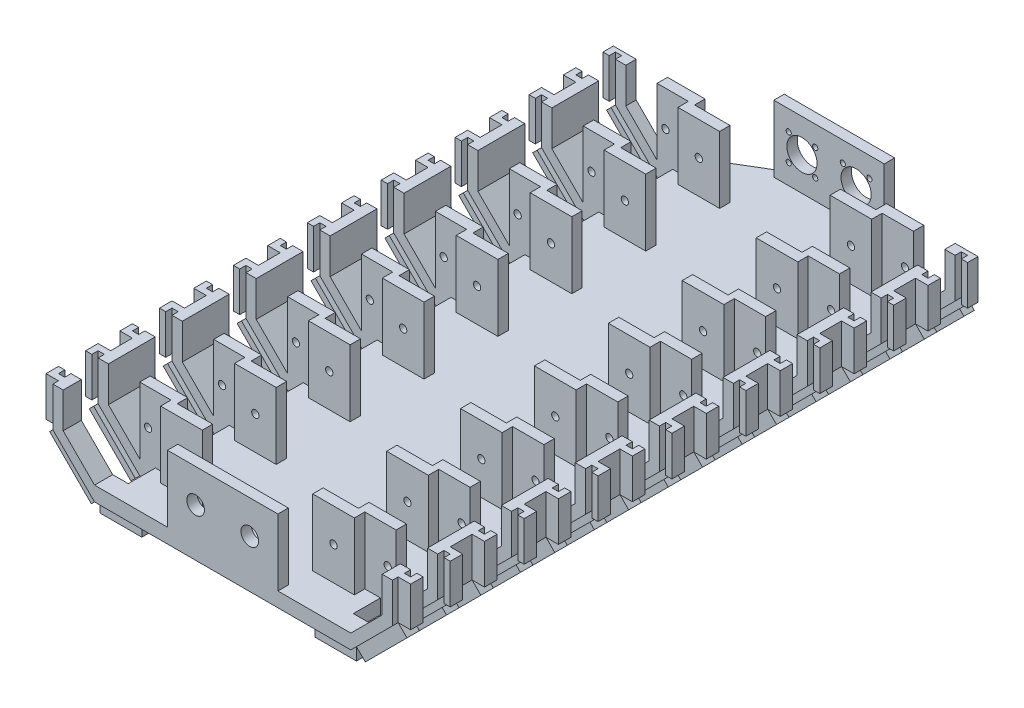
SolidWorks part; units mm, degrees
ref_plane "Front Plane" through (0, 0, 0) normal (0, 0, 1) x (1, 0, 0)
ref_plane "Top Plane" through (0, 0, 0) normal (0, 1, 0) x (1, 0, 0)
ref_plane "Right Plane" through (0, 0, 0) normal (1, 0, 0) x (0, 0, -1)
sketch "Sketch1" plane through (0, 0, 0) normal (0, 1, 0) x (1, 0, 0)
  line L0 (0, -135) -> (0, 135) construction
  line L1 (-13, 135) -> (-36, 135)
  line L2 (13, -135) -> (-13, -135)
  line L3 (13, -135) -> (13, 135) construction
  line L4 (13, 135) -> (-13, 135)
  line L5 (-13, -135) -> (-13, 135) construction
  line L8 (-36, 135) -> (-36, -135) construction
  line L9 (-36, -135) -> (-13, -135)
  line L10 (-36, 135) -> (-61.5, 135)
  line L11 (-61.5, 135) -> (-61.5, -135)
  line L12 (-61.5, -135) -> (-36, -135)
  line L13 (36, -135) -> (13, -135)
  line L14 (61.5, -135) -> (36, -135)
  line L15 (61.5, 135) -> (61.5, -135)
  line L16 (36, 135) -> (36, -135) construction
  line L17 (13, 135) -> (36, 135)
  line L18 (36, 135) -> (61.5, 135)
  point P0 (0, 0)
  point P4 (0, 0)
  dimension "D1" = 270
  dimension "D2" = 26
  dimension "D3" = 23
  dimension "D4" = 123
extrude "Boss-Extrude1" add sketch "Sketch1" along normal blind 7
sketch "Sketch2" plane through (0, 7, 0) normal (0, 1, 0) x (1, 0, 0)
  line L0 (61.5, -135) -> (61.5, 135) construction
  line L1 (-61.5, -135) -> (61.5, -135)
  line L2 (-61.5, -135) -> (-61.5, -130)
  line L3 (-61.5, -130) -> (61.5, -130)
  line L4 (61.5, -135) -> (61.5, -130)
  line L5 (-61.5, 135) -> (-36.5, 135) construction
  line L6 (-61.5, 135) -> (61.5, 135) construction
  line L7 (-61.5, 135) -> (-61.5, 130) construction
  line L8 (-61.5, 130) -> (61.5, 130) construction
  line L9 (61.5, 135) -> (61.5, 130) construction
  line L10 (-36.5, 135) -> (-26.5, 135)
  line L11 (-36.5, 135) -> (-46.5, 135)
  line L12 (-46.5, 135) -> (-46.5, 130)
  line L13 (-46.5, 130) -> (-26.5, 130)
  line L14 (-26.5, 130) -> (-26.5, 135)
  line L15 (0, 135) -> (0, 130) construction
  line L16 (46.5, 130) -> (26.5, 130)
  line L17 (46.5, 135) -> (46.5, 130)
  line L18 (36.5, 135) -> (46.5, 135)
  line L19 (36.5, 135) -> (26.5, 135)
  line L20 (26.5, 130) -> (26.5, 135)
  line L21 (-26.5, 130) -> (-26.5, -130) construction
  dimension "D1" = 5
  dimension "D2" = 5
  dimension "D3" = 25
  dimension "D4" = 10
  dimension "D5" = 10
extrude "Boss-Extrude2" add sketch "Sketch2" along normal blind 32
sketch "Sketch3" plane through (0, 0, 135) normal (0, 0, 1) x (1, 0, 0)
  line L0 (0, 39) -> (0, 0) construction
  line L2 (-61.5, 39) -> (-61.5, 7) construction
  line L3 (-61.5, 39) -> (61.5, 39) construction
  line L5 (-61.5, 39) -> (-61.5, 0) construction
  line L6 (-61.5, 23) -> (61.5, 23) construction
  line L7 (61.5, 39) -> (61.5, 0) construction
  circle A0 centre (-13, 23) radius 4.25
  circle A1 centre (13, 23) radius 4.25
  dimension "D1" = 8.5
  dimension "D2" = 8.5
  dimension "D3" = 26
  dimension "D4" = 13
  dimension "D5" = 32
  dimension "D6" = 16
sketch "Sketch8" plane through (0, 0, -130) normal (0, 0, 1) x (1, 0, 0)
  line L0 (0, 39) -> (0, 7) construction
  line L2 (0, 23) -> (-61.5, 23) construction
  line L3 (-61.5, 39) -> (-61.5, 0) construction
  line L4 (-36.5, 39) -> (-36.5, 7) construction
  line L5 (-46.5, 39) -> (-26.5, 39) construction
  line L6 (-46.5, 7) -> (-26.5, 7) construction
  line L7 (-61.5, 39) -> (61.5, 39) construction
  circle A0 centre (-36.5, 23) radius 1.75
  circle A1 centre (36.5, 23) radius 1.75
  dimension "D2" = 3.5
  dimension "D1" = 32
sketch "Sketch9" plane through (0, 0, -135) normal (0, 0, -1) x (-1, 0, 0)
  line L1 (-61.5, 7) -> (61.5, 7)
  line L2 (-61.5, 7) -> (-61.5, 0)
  line L3 (-61.5, 0) -> (61.5, 0)
  line L4 (61.5, 7) -> (61.5, 0)
extrude "Boss-Extrude4" add sketch "Sketch9" along normal blind 5
sketch "Sketch10" plane through (0, 7, 0) normal (0, 1, 0) x (1, 0, 0)
  line L0 (-26.5, 135) -> (-46.5, 135) construction
  line L1 (-61.5, 140) -> (-43.5, 140)
  line L2 (-61.5, 140) -> (-61.5, 135)
  line L3 (-61.5, 135) -> (-43.5, 135)
  line L4 (-43.5, 140) -> (-43.5, 135)
  line L5 (26.5, 135) -> (46.5, 135) construction
  line L6 (61.5, 140) -> (43.5, 140)
  line L7 (61.5, 140) -> (61.5, 135)
  line L8 (61.5, 135) -> (43.5, 135)
  line L9 (43.5, 140) -> (43.5, 135)
  line L10 (-46.5, 135) -> (-46.5, 130) construction
  line L11 (46.5, 130) -> (46.5, 135) construction
  dimension "D1" = 3
  dimension "D2" = 3
extrude "Boss-Extrude8" add sketch "Sketch10" along normal blind 32
sketch "Sketch11" plane through (0, 7, 0) normal (0, 1, 0) x (1, 0, 0)
  line L0 (0, 140) -> (0, -130) construction
  line L1 (-43.5, 140) -> (43.5, 140) construction
  line L2 (61.5, -130) -> (-61.5, -130) construction
  line L3 (-61.5, 140) -> (-61.5, 135) construction
  line L4 (-61.5, 135) -> (-46.5, 135) construction
  line L5 (-46.5, 135) -> (-46.5, 130) construction
  line L6 (-46.5, 130) -> (-26.5, 130) construction
  line L7 (-26.5, 130) -> (-26.5, 135) construction
  line L8 (-26.5, 135) -> (-43.5, 135) construction
  line L9 (-43.5, 135) -> (-43.5, 140) construction
  line L10 (-43.5, 140) -> (-61.5, 140) construction
  line L11 (-26.5, -130) -> (-26.5, -109.8199)
  line L12 (-43.5, 104.5294) -> (-61.5, 104.5294)
  line L13 (-61.5, 104.5294) -> (-61.5, 99.5294)
  line L14 (-61.5, 99.5294) -> (-46.5, 99.5294)
  line L15 (-46.5, 99.5294) -> (-46.5, 94.5294)
  line L16 (-46.5, 94.5294) -> (-26.5, 94.5294)
  line L17 (-26.5, 94.5294) -> (-26.5, 99.5294)
  line L18 (-26.5, 99.5294) -> (-43.5, 99.5294)
  line L19 (-43.5, 99.5294) -> (-43.5, 104.5294)
  line L20 (-43.5, 69.0588) -> (-61.5, 69.0588)
  line L21 (-61.5, 69.0588) -> (-61.5, 64.0588)
  line L22 (-61.5, 64.0588) -> (-46.5, 64.0588)
  line L23 (-46.5, 64.0588) -> (-46.5, 59.0588)
  line L24 (-46.5, 59.0588) -> (-26.5, 59.0588)
  line L25 (-26.5, 59.0588) -> (-26.5, 64.0588)
  line L26 (-26.5, 64.0588) -> (-43.5, 64.0588)
  line L27 (-43.5, 64.0588) -> (-43.5, 69.0588)
  line L28 (-43.5, 33.5882) -> (-61.5, 33.5882)
  line L29 (-61.5, 33.5882) -> (-61.5, 28.5882)
  line L30 (-61.5, 28.5882) -> (-46.5, 28.5882)
  line L31 (-46.5, 28.5882) -> (-46.5, 23.5882)
  line L32 (-46.5, 23.5882) -> (-26.5, 23.5882)
  line L33 (-26.5, 23.5882) -> (-26.5, 28.5882)
  line L34 (-26.5, 28.5882) -> (-43.5, 28.5882)
  line L35 (-43.5, 28.5882) -> (-43.5, 33.5882)
  line L36 (-43.5, -1.8824) -> (-61.5, -1.8824)
  line L37 (-61.5, -1.8824) -> (-61.5, -6.8824)
  line L38 (-61.5, -6.8824) -> (-46.5, -6.8824)
  line L39 (-46.5, -6.8824) -> (-46.5, -11.8824)
  line L40 (-46.5, -11.8824) -> (-26.5, -11.8824)
  line L41 (-26.5, -11.8824) -> (-26.5, -6.8824)
  line L42 (-26.5, -6.8824) -> (-43.5, -6.8824)
  line L43 (-43.5, -6.8824) -> (-43.5, -1.8824)
  line L44 (-43.5, -37.3529) -> (-61.5, -37.3529)
  line L45 (-61.5, -37.3529) -> (-61.5, -42.3529)
  line L46 (-61.5, -42.3529) -> (-46.5, -42.3529)
  line L47 (-46.5, -42.3529) -> (-46.5, -47.3529)
  line L48 (-46.5, -47.3529) -> (-26.5, -47.3529)
  line L49 (-26.5, -47.3529) -> (-26.5, -42.3529)
  line L50 (-26.5, -42.3529) -> (-43.5, -42.3529)
  line L51 (-43.5, -42.3529) -> (-43.5, -37.3529)
  line L52 (-43.5, -72.8235) -> (-61.5, -72.8235)
  line L53 (-61.5, -72.8235) -> (-61.5, -77.8235)
  line L54 (-61.5, -77.8235) -> (-46.5, -77.8235)
  line L55 (-46.5, -77.8235) -> (-46.5, -82.8235)
  line L56 (-46.5, -82.8235) -> (-26.5, -82.8235)
  line L57 (-26.5, -82.8235) -> (-26.5, -77.8235)
  line L58 (-26.5, -77.8235) -> (-43.5, -77.8235)
  line L59 (-43.5, -77.8235) -> (-43.5, -72.8235)
  line L60 (-43.5, -108.2941) -> (-61.5, -108.2941)
  line L61 (-61.5, -108.2941) -> (-61.5, -113.2941)
  line L62 (-61.5, -113.2941) -> (-46.5, -113.2941)
  line L63 (-46.5, -113.2941) -> (-46.5, -118.2941)
  line L64 (-46.5, -118.2941) -> (-26.5, -118.2941)
  line L65 (-26.5, -118.2941) -> (-26.5, -113.2941)
  line L66 (-26.5, -113.2941) -> (-43.5, -113.2941)
  line L67 (-43.5, -113.2941) -> (-43.5, -108.2941)
  line L68 (43.5, -113.2941) -> (43.5, -108.2941)
  line L69 (26.5, -113.2941) -> (43.5, -113.2941)
  line L70 (26.5, -118.2941) -> (26.5, -113.2941)
  line L71 (46.5, -118.2941) -> (26.5, -118.2941)
  line L72 (46.5, -113.2941) -> (46.5, -118.2941)
  line L73 (61.5, -113.2941) -> (46.5, -113.2941)
  line L74 (61.5, -108.2941) -> (61.5, -113.2941)
  line L75 (43.5, -108.2941) -> (61.5, -108.2941)
  line L76 (43.5, -77.8235) -> (43.5, -72.8235)
  line L77 (26.5, -77.8235) -> (43.5, -77.8235)
  line L78 (26.5, -82.8235) -> (26.5, -77.8235)
  line L79 (46.5, -82.8235) -> (26.5, -82.8235)
  line L80 (46.5, -77.8235) -> (46.5, -82.8235)
  line L81 (61.5, -77.8235) -> (46.5, -77.8235)
  line L82 (61.5, -72.8235) -> (61.5, -77.8235)
  line L83 (43.5, -72.8235) -> (61.5, -72.8235)
  line L84 (43.5, -42.3529) -> (43.5, -37.3529)
  line L85 (26.5, -42.3529) -> (43.5, -42.3529)
  line L86 (26.5, -47.3529) -> (26.5, -42.3529)
  line L87 (46.5, -47.3529) -> (26.5, -47.3529)
  line L88 (46.5, -42.3529) -> (46.5, -47.3529)
  line L89 (61.5, -42.3529) -> (46.5, -42.3529)
  line L90 (61.5, -37.3529) -> (61.5, -42.3529)
  line L91 (43.5, -37.3529) -> (61.5, -37.3529)
  line L92 (43.5, -6.8824) -> (43.5, -1.8824)
  line L93 (26.5, -6.8824) -> (43.5, -6.8824)
  line L94 (26.5, -11.8824) -> (26.5, -6.8824)
  line L95 (46.5, -11.8824) -> (26.5, -11.8824)
  line L96 (46.5, -6.8824) -> (46.5, -11.8824)
  line L97 (61.5, -6.8824) -> (46.5, -6.8824)
  line L98 (61.5, -1.8824) -> (61.5, -6.8824)
  line L99 (43.5, -1.8824) -> (61.5, -1.8824)
  line L100 (43.5, 28.5882) -> (43.5, 33.5882)
  line L101 (26.5, 28.5882) -> (43.5, 28.5882)
  line L102 (26.5, 23.5882) -> (26.5, 28.5882)
  line L103 (46.5, 23.5882) -> (26.5, 23.5882)
  line L104 (46.5, 28.5882) -> (46.5, 23.5882)
  line L105 (61.5, 28.5882) -> (46.5, 28.5882)
  line L106 (61.5, 33.5882) -> (61.5, 28.5882)
  line L107 (43.5, 33.5882) -> (61.5, 33.5882)
  line L108 (43.5, 64.0588) -> (43.5, 69.0588)
  line L109 (26.5, 64.0588) -> (43.5, 64.0588)
  line L110 (26.5, 59.0588) -> (26.5, 64.0588)
  line L111 (46.5, 59.0588) -> (26.5, 59.0588)
  line L112 (46.5, 64.0588) -> (46.5, 59.0588)
  line L113 (61.5, 64.0588) -> (46.5, 64.0588)
  line L114 (61.5, 69.0588) -> (61.5, 64.0588)
  line L115 (43.5, 69.0588) -> (61.5, 69.0588)
  line L116 (43.5, 99.5294) -> (43.5, 104.5294)
  line L117 (26.5, 99.5294) -> (43.5, 99.5294)
  line L118 (26.5, 94.5294) -> (26.5, 99.5294)
  line L119 (46.5, 94.5294) -> (26.5, 94.5294)
  line L120 (46.5, 99.5294) -> (46.5, 94.5294)
  line L121 (61.5, 99.5294) -> (46.5, 99.5294)
  line L122 (61.5, 104.5294) -> (61.5, 99.5294)
  line L123 (43.5, 104.5294) -> (61.5, 104.5294)
  point P136 (-54, 135)
  line M11 (-61.5, 135) -> (-61.5, -130)
  line M13 (61.5, -130) -> (61.5, 135)
  dimension "D1" = 20.1801
  dimension "D3" = 30.4706
  dimension "D2" = 8
extrude "Boss-Extrude9" add sketch "Sketch11" along normal blind 32 contours L18 L19 L12 L14 L15 L16 L17 M11 | L26 L27 L20 L22 L23 L24 L25 M11 | L34 L35 L28 L30 L31 L32 L33 M11 | L42 L43 L36 L38 L39 L40 L41 M11 | L50 L51 L44 L46 L47 L48 L49 M11 | L58 L59 L52 L54 L55 L56 L57 M11 | L66 L67 L60 L62 L63 L64 L11 M11 | L75 L68 L69 L70 L71 L72 L73 M13 | L83 L76 L77 L78 L79 L80 L81 M13 | L91 L84 L85 L86 L87 L88 L89 M13 | L107 L100 L101 L102 L103 L104 L105 M13 | L115 L108 L109 L110 L111 L112 L113 M13 | L123 L116 L117 L118 L119 L120 L121 M13 | L93 L92 L99 L98 L97 L96 L95 L94 region at (-44.0789, 7, 113.4257) region at (-44.0789, 7, -99.3978) region at (-44.0789, 7, -63.9272) region at (-44.0789, 7, -28.4567) region at (-44.0789, 7, 7.0139) region at (-44.0789, 7, 42.4845) region at (-44.0789, 7, 77.9551) region at (44.0789, 7, -99.3978) region at (44.0789, 7, -63.9272) region at (44.0789, 7, -28.4567) region at (44.0789, 7, 42.4845) region at (44.0789, 7, 77.9551) region at (44.0789, 7, 113.4257)
extrude "Cut-Extrude4" cut sketch "Sketch8" against normal blind 32 and the other way blind 250
sketch "Sketch13" plane through (0, 0, 135) normal (0, 0, 1) x (1, 0, 0)
  line L0 (-61.5, 39) -> (-61.5, 7)
  line L1 (-61.5, 39) -> (-61.5, 0) construction
  line L2 (-61.5, 39) -> (-26.5, 39)
  line L3 (-61.5, 39) -> (61.5, 39) construction
  line L4 (-26.5, 39) -> (-26.5, 7)
  line L5 (-26.5, 7) -> (-61.5, 7)
  line L6 (0, 39) -> (0, 5.5161) construction
  line L7 (26.5, 39) -> (26.5, 7)
  line L8 (61.5, 39) -> (26.5, 39)
  line L9 (61.5, 39) -> (61.5, 7)
  line L10 (26.5, 7) -> (61.5, 7)
  dimension "D1" = 32
  dimension "D2" = 35
extrude "Cut-Extrude5" cut sketch "Sketch13" against normal blind 11
sketch "Sketch14" plane through (0, 0, 135) normal (0, 0, 1) x (1, 0, 0)
  line L0 (0, 39) -> (0, 0) construction
  line L1 (-26.5, 39) -> (26.5, 39) construction
  line L2 (-81.5, 39) -> (0, 39) construction
  line L3 (-61.5, 0) -> (-81.5, 20)
  line L5 (-76.55, 22.05) -> (-61.5, 7)
  line L6 (-61.5, 39) -> (-61.5, 7) construction
  line L7 (-61.5, 7) -> (-61.5, 0)
  line L12 (-81.5, 20) -> (-81.5, 39)
  line L13 (-81.5, 39) -> (-76.55, 39)
  line L14 (-76.55, 39) -> (-76.55, 22.05)
  line L15 (76.55, 39) -> (76.55, 22.05)
  line L16 (81.5, 39) -> (76.55, 39)
  line L17 (81.5, 20) -> (81.5, 39)
  line L18 (61.5, 0) -> (81.5, 20)
  line L19 (61.5, 7) -> (61.5, 0)
  line L20 (76.55, 22.05) -> (61.5, 7)
  dimension "D1" = 28.2843
  dimension "D2" = 45
  dimension "D3" = 4.95
  dimension "D4" = 20
  dimension "D5" = 4.9497
extrude "Boss-Extrude10" add sketch "Sketch14" against normal blind 275
sketch "Sketch15" plane through (0, 7, 0) normal (0, 1, 0) x (1, 0, 0)
  line L0 (-54, 135) -> (-54, 122)
  line L1 (-61.5, 135) -> (-46.5, 135) construction
  line L2 (-54, 122) -> (-81.5, 122)
  line L4 (-81.5, 122) -> (-81.5, 135)
  line L5 (-81.5, 135) -> (-54, 135)
  line L6 (-81.5, 99.5294) -> (-54, 99.5294)
  line L7 (-54, 99.5294) -> (-54, 86.5294)
  line L8 (-54, 86.5294) -> (-81.5, 86.5294)
  line L9 (-81.5, 86.5294) -> (-81.5, 99.5294)
  line L10 (-81.5, 64.0588) -> (-54, 64.0588)
  line L11 (-54, 64.0588) -> (-54, 51.0588)
  line L12 (-54, 51.0588) -> (-81.5, 51.0588)
  line L13 (-81.5, 51.0588) -> (-81.5, 64.0588)
  line L14 (-81.5, 28.5882) -> (-54, 28.5882)
  line L15 (-54, 28.5882) -> (-54, 15.5882)
  line L16 (-54, 15.5882) -> (-81.5, 15.5882)
  line L17 (-81.5, 15.5882) -> (-81.5, 28.5882)
  line L18 (-81.5, -6.8824) -> (-54, -6.8824)
  line L19 (-54, -6.8824) -> (-54, -19.8824)
  line L20 (-54, -19.8824) -> (-81.5, -19.8824)
  line L21 (-81.5, -19.8824) -> (-81.5, -6.8824)
  line L22 (-81.5, -42.3529) -> (-54, -42.3529)
  line L23 (-54, -42.3529) -> (-54, -55.3529)
  line L24 (-54, -55.3529) -> (-81.5, -55.3529)
  line L25 (-81.5, -55.3529) -> (-81.5, -42.3529)
  line L26 (-81.5, -77.8235) -> (-54, -77.8235)
  line L27 (-54, -77.8235) -> (-54, -90.8235)
  line L28 (-54, -90.8235) -> (-81.5, -90.8235)
  line L29 (-81.5, -90.8235) -> (-81.5, -77.8235)
  line L30 (-81.5, -113.2941) -> (-54, -113.2941)
  line L31 (-54, -113.2941) -> (-54, -126.2941)
  line L32 (-54, -126.2941) -> (-81.5, -126.2941)
  line L33 (-81.5, -126.2941) -> (-81.5, -113.2941)
  line L34 (0, 140) -> (0, -135) construction
  line L35 (-43.5, 140) -> (43.5, 140) construction
  line L36 (-26.5, -135) -> (26.5, -135) construction
  line L37 (81.5, -126.2941) -> (81.5, -113.2941)
  line L38 (54, -126.2941) -> (81.5, -126.2941)
  line L39 (54, -113.2941) -> (54, -126.2941)
  line L40 (81.5, -113.2941) -> (54, -113.2941)
  line L41 (81.5, -90.8235) -> (81.5, -77.8235)
  line L42 (54, -90.8235) -> (81.5, -90.8235)
  line L43 (54, -77.8235) -> (54, -90.8235)
  line L44 (81.5, -77.8235) -> (54, -77.8235)
  line L45 (81.5, -55.3529) -> (81.5, -42.3529)
  line L46 (54, -55.3529) -> (81.5, -55.3529)
  line L47 (54, -42.3529) -> (54, -55.3529)
  line L48 (81.5, -42.3529) -> (54, -42.3529)
  line L49 (81.5, -19.8824) -> (81.5, -6.8824)
  line L50 (54, -19.8824) -> (81.5, -19.8824)
  line L51 (54, -6.8824) -> (54, -19.8824)
  line L52 (81.5, -6.8824) -> (54, -6.8824)
  line L53 (81.5, 15.5882) -> (81.5, 28.5882)
  line L54 (54, 15.5882) -> (81.5, 15.5882)
  line L55 (54, 28.5882) -> (54, 15.5882)
  line L56 (81.5, 28.5882) -> (54, 28.5882)
  line L57 (81.5, 51.0588) -> (81.5, 64.0588)
  line L58 (54, 51.0588) -> (81.5, 51.0588)
  line L59 (54, 64.0588) -> (54, 51.0588)
  line L60 (81.5, 64.0588) -> (54, 64.0588)
  line L61 (81.5, 86.5294) -> (81.5, 99.5294)
  line L62 (54, 86.5294) -> (81.5, 86.5294)
  line L63 (54, 99.5294) -> (54, 86.5294)
  line L64 (81.5, 99.5294) -> (54, 99.5294)
  line L65 (81.5, 122) -> (81.5, 135)
  line L66 (54, 122) -> (81.5, 122)
  line L67 (54, 135) -> (54, 122)
  line L68 (81.5, 135) -> (54, 135)
  line L69 (-61.5, -113.2941) -> (-46.5, -113.2941) construction
  line L70 (-81.5, 140) -> (-81.5, -135) construction
  dimension "D1" = 13
  dimension "D2" = 8
extrude "Cut-Extrude6" cut sketch "Sketch15" against normal through all both and the other way through all
sketch "Sketch16" plane through (0, 0, 113.2941) normal (0, 0, 1) x (1, 0, 0)
  line L0 (-61.5, 23) -> (0, 23) construction
  line L1 (-61.5, 39) -> (-61.5, 7) construction
  line L2 (0, 39) -> (0, 0) construction
  line L3 (-26.5, 39) -> (26.5, 39) construction
  circle A0 centre (-57.5, 22) radius 1.75
  circle A1 centre (57.5, 22) radius 1.75
  point P9 (-36.5, 23)
  dimension "D3" = 3.5
  dimension "D1" = 1
  dimension "D2" = 21
extrude "Cut-Extrude7" cut sketch "Sketch16" against normal through all both and the other way through all
sketch "Sketch17" plane through (0, 7, 0) normal (0, 1, 0) x (1, 0, 0)
  line L0 (-26.5, 130) -> (26.5, 130) construction
  line L1 (0, 130) -> (0, 161) construction
  line L2 (-26.5, -135) -> (-26.5, 161) construction
  line L3 (26.5, -135) -> (26.5, 161) construction
  line L4 (26.5, 161) -> (-26.5, 161) construction
  line L5 (0, 161) -> (0, 226) construction
  line L6 (-61.5, 140) -> (-26.5, 226)
  line L7 (-26.5, 226) -> (0, 226)
  line L8 (0, 226) -> (26.5, 226)
  line L9 (26.5, 226) -> (61.5, 140)
  line L10 (26.5, 161) -> (26.5, 226) construction
  line L11 (-26.5, 161) -> (-26.5, 226) construction
  line L12 (-61.5, 140) -> (61.5, 140)
  dimension "D1" = 31
  dimension "D2" = 296
  dimension "D3" = 90
  dimension "D4" = 65
extrude "Boss-Extrude13" add sketch "Sketch17" against normal blind 7 contours L12 L9 L8 L7 L6
sketch "Sketch18" plane through (0, 7, 0) normal (0, 1, 0) x (1, 0, 0)
  line L0 (-26.5, 130) -> (26.5, 130) construction
  line L1 (0, 130) -> (0, 161) construction
  line L2 (-26.5, 135) -> (-26.5, 161) construction
  line L3 (26.5, 135) -> (26.5, 161) construction
  line L4 (-26.5, 161) -> (-26.5, 156)
  line L5 (-26.5, 156) -> (26.5, 156)
  line L6 (26.5, 156) -> (26.5, 161)
  line L7 (26.5, 161) -> (-26.5, 161)
  dimension "D1" = 31
  dimension "D2" = 5
extrude "Boss-Extrude14" add sketch "Sketch18" along normal blind 32
extrude "Cut-Extrude8" cut sketch "Sketch3" against normal blind 334
sketch "Sketch19" plane through (0, 0, -156) normal (0, 0, 1) x (1, 0, 0)
  line L0 (0, 39) -> (0, 0) construction
  line L1 (-26.5, 39) -> (26.5, 39) construction
  line L3 (-6.636, 16.636) -> (-19.364, 16.636) construction
  line L4 (-6.636, 16.636) -> (-6.636, 29.364) construction
  line L5 (-6.636, 29.364) -> (-19.364, 29.364) construction
  line L6 (-19.364, 16.636) -> (-19.364, 29.364) construction
  line L7 (-6.636, 16.636) -> (-19.364, 29.364) construction
  line L8 (-6.636, 29.364) -> (-19.364, 16.636) construction
  circle A0 centre (-13, 23) radius 7.25
  circle A1 centre (-6.636, 16.636) radius 1.25
  circle A2 centre (-6.636, 29.364) radius 1.25
  circle A3 centre (-19.364, 29.364) radius 1.25
  circle A4 centre (-19.364, 16.636) radius 1.25
  circle A5 centre (13, 23) radius 7.25
  circle A6 centre (19.364, 16.636) radius 1.25
  circle A7 centre (6.636, 16.636) radius 1.25
  circle A8 centre (6.636, 29.364) radius 1.25
  circle A9 centre (19.364, 29.364) radius 1.25
  dimension "D1" = 14.5
  dimension "D4" = 2.5
  dimension "D5" = 2.5
  dimension "D6" = 2.5
  dimension "D7" = 2.5
  dimension "D2" = 18
  dimension "D3" = 18
  dimension "D8" = 12.7279
extrude "Cut-Extrude9" cut sketch "Sketch19" against normal blind 334
sketch "Sketch22" plane through (-30.75, -30.75, 0) normal (-0.7071, -0.7071, 0) x (0, 0, 1)
  line L0 (-138, 71.7713) -> (-138, 43.4871)
  line L1 (-140, 71.7713) -> (-135, 71.7713) construction
  line L2 (-140, 43.4871) -> (-135, 43.4871) construction
  line L3 (-140, 71.7713) -> (-140, 43.4871)
  line L4 (-135, 71.7713) -> (-135, 43.4871) construction
  line L5 (-138, 71.7713) -> (-140, 71.7713)
  line L6 (-140, 43.4871) -> (-226, 18.7383) construction
  line L7 (-140, 43.4871) -> (-138, 43.4871)
  line L8 (-119, 71.7713) -> (-119, 43.4871)
  line L9 (-122, 71.7713) -> (-99.5294, 71.7713) construction
  line L10 (-122, 43.4871) -> (-99.5294, 43.4871) construction
  line L11 (-119, 43.4871) -> (-116, 43.4871)
  line L12 (-116, 43.4871) -> (-116, 71.7713)
  line L13 (-116, 71.7713) -> (-119, 71.7713)
  line L14 (-122, 43.4871) -> (-122, 71.7713) construction
  line L15 (-99.5294, 71.7713) -> (-102.5294, 71.7713)
  line L16 (-102.5294, 71.7713) -> (-105.5294, 71.7713)
  line L17 (-105.5294, 71.7713) -> (-105.5294, 43.4871)
  line L18 (-105.5294, 43.4871) -> (-102.5294, 43.4871)
  line L19 (-102.5294, 43.4871) -> (-102.5294, 71.7713)
  line L20 (-86.5294, 71.7713) -> (-83.5294, 71.7713)
  line L21 (-86.5294, 71.7713) -> (-64.0588, 71.7713) construction
  line L22 (-83.5294, 71.7713) -> (-80.5294, 71.7713)
  line L23 (-80.5294, 71.7713) -> (-80.5294, 43.4871)
  line L24 (-86.5294, 43.4871) -> (-64.0588, 43.4871) construction
  line L25 (-80.5294, 43.4871) -> (-83.5294, 43.4871)
  line L26 (-83.5294, 43.4871) -> (-83.5294, 71.7713)
  line L27 (-67.0588, 71.7713) -> (-70.0588, 71.7713)
  line L28 (-70.0588, 71.7713) -> (-70.0588, 43.4871)
  line L29 (-70.0588, 43.4871) -> (-67.0588, 43.4871)
  line L30 (-67.0588, 43.4871) -> (-67.0588, 71.7713)
  line L31 (-48.0588, 71.7713) -> (-45.0588, 71.7713)
  line L32 (-45.0588, 71.7713) -> (-45.0588, 43.4871)
  line L33 (-45.0588, 43.4871) -> (-48.0588, 43.4871)
  line L34 (-48.0588, 43.4871) -> (-48.0588, 71.7713)
  line L35 (-31.5882, 71.7713) -> (-34.5882, 71.7713)
  line L36 (-34.5882, 71.7713) -> (-34.5882, 43.4871)
  line L37 (-34.5882, 43.4871) -> (-31.5882, 43.4871)
  line L38 (-31.5882, 43.4871) -> (-31.5882, 71.7713)
  line L39 (-12.5882, 71.7713) -> (-9.5882, 71.7713)
  line L40 (-9.5882, 71.7713) -> (-9.5882, 43.4871)
  line L41 (-9.5882, 43.4871) -> (-12.5882, 43.4871)
  line L42 (-12.5882, 43.4871) -> (-12.5882, 71.7713)
  line L43 (3.8824, 71.7713) -> (0.8824, 71.7713)
  line L44 (0.8824, 71.7713) -> (0.8824, 43.4871)
  line L45 (0.8824, 43.4871) -> (3.8824, 43.4871)
  line L46 (3.8824, 43.4871) -> (3.8824, 71.7713)
  line L47 (22.8824, 71.7713) -> (25.8824, 71.7713)
  line L48 (25.8824, 71.7713) -> (25.8824, 43.4871)
  line L49 (25.8824, 43.4871) -> (22.8824, 43.4871)
  line L50 (22.8824, 43.4871) -> (22.8824, 71.7713)
  line L51 (39.3529, 71.7713) -> (36.3529, 71.7713)
  line L52 (36.3529, 71.7713) -> (36.3529, 43.4871)
  line L53 (36.3529, 43.4871) -> (39.3529, 43.4871)
  line L54 (39.3529, 43.4871) -> (39.3529, 71.7713)
  line L55 (58.3529, 71.7713) -> (61.3529, 71.7713)
  line L56 (61.3529, 71.7713) -> (61.3529, 43.4871)
  line L57 (61.3529, 43.4871) -> (58.3529, 43.4871)
  line L58 (58.3529, 43.4871) -> (58.3529, 71.7713)
  line L59 (74.8235, 71.7713) -> (71.8235, 71.7713)
  line L60 (71.8235, 71.7713) -> (71.8235, 43.4871)
  line L61 (71.8235, 43.4871) -> (74.8235, 43.4871)
  line L62 (74.8235, 43.4871) -> (74.8235, 71.7713)
  line L63 (93.8235, 71.7713) -> (96.8235, 71.7713)
  line L64 (96.8235, 71.7713) -> (96.8235, 43.4871)
  line L65 (96.8235, 43.4871) -> (93.8235, 43.4871)
  line L66 (93.8235, 43.4871) -> (93.8235, 71.7713)
  line L67 (110.2941, 71.7713) -> (107.2941, 71.7713)
  line L68 (107.2941, 71.7713) -> (107.2941, 43.4871)
  line L69 (107.2941, 43.4871) -> (110.2941, 43.4871)
  line L70 (110.2941, 43.4871) -> (110.2941, 71.7713)
  line L71 (129.2941, 71.7713) -> (132.2941, 71.7713)
  line L72 (132.2941, 71.7713) -> (132.2941, 43.4871)
  line L73 (132.2941, 43.4871) -> (129.2941, 43.4871)
  line L74 (129.2941, 43.4871) -> (129.2941, 71.7713)
  line L75 (129.2941, 71.7713) -> (129.2941, 43.4871) construction
  line L76 (126.2941, 71.7713) -> (135, 71.7713) construction
  line L77 (126.2941, 43.4871) -> (135, 43.4871) construction
  line L78 (126.2941, 43.4871) -> (126.2941, 71.7713) construction
  line M20 (-135, 71.7713) -> (-140, 71.7713)
  line M21 (-140, 71.7713) -> (-140, 43.4871)
  line M22 (-140, 43.4871) -> (-135, 43.4871)
  dimension "D1" = 3
  dimension "D2" = 3
  dimension "D3" = 3
  dimension "D4" = 3
  dimension "D5" = 3
  dimension "D6" = 3
  dimension "D7" = 3
  dimension "D9" = 3
  dimension "D10" = 3
  dimension "D8" = 7
extrude "Boss-Extrude15" add sketch "Sketch22" along normal blind 3 contours L0 M20 M21 M22 | L12 L13 L8 L11 | L18 L19 L16 L17 | L26 L25 L23 L22 | L29 L30 L27 L28 | L34 L33 L32 L31 | L37 L38 L35 L36 | L45 L46 L43 L44 | L50 L49 L48 L47 | L53 L54 L51 L52 | L58 L57 L56 L55 | L61 L62 L59 L60 | L66 L65 L64 L63 | L69 L70 L67 L68 | L74 L73 L72 L71 | L42 L39 L40 L41 region at (-71.5, 10, -139) region at (-71.5, 10, -117.5) region at (-71.5, 10, -104.0294) region at (-71.5, 10, -82.0294) region at (-71.5, 10, -68.5588) region at (-71.5, 10, -46.5588) region at (-71.5, 10, -33.0882) region at (-71.5, 10, 2.3824) region at (-71.5, 10, 24.3824) region at (-71.5, 10, 37.8529) region at (-71.5, 10, 59.8529) region at (-71.5, 10, 73.3235) region at (-71.5, 10, 95.3235) region at (-71.5, 10, 108.7941) region at (-71.5, 10, 130.7941)
sketch "Sketch23" plane through (-32.8713, -32.8713, 0) normal (-0.7071, -0.7071, 0) x (0, 0, 1)
  line L0 (-140, 71.7713) -> (-135, 71.7713)
  line L2 (-140, 71.7713) -> (-140, 43.4871)
  line L4 (-116, 71.7713) -> (-116, 43.4871)
  line L5 (-135, 71.7713) -> (-135, 43.4871)
  line L6 (-135, 43.4871) -> (-140, 43.4871)
  line L7 (-116, 71.7713) -> (-122, 71.7713)
  line L8 (-122, 71.7713) -> (-122, 43.4871)
  line L9 (-122, 43.4871) -> (-116, 43.4871)
  line L10 (-99.5294, 71.7713) -> (-105.5294, 71.7713)
  line L11 (-105.5294, 71.7713) -> (-105.5294, 43.4871)
  line L12 (-105.5294, 43.4871) -> (-99.5294, 43.4871)
  line L13 (-99.5294, 43.4871) -> (-99.5294, 71.7713)
  line L14 (-80.5294, 71.7713) -> (-86.5294, 71.7713)
  line L15 (-86.5294, 71.7713) -> (-86.5294, 43.4871)
  line L16 (-86.5294, 43.4871) -> (-80.5294, 43.4871)
  line L17 (-80.5294, 43.4871) -> (-80.5294, 71.7713)
  line L18 (-64.0588, 43.4871) -> (-64.0588, 71.7713)
  line L19 (-64.0588, 71.7713) -> (-70.0588, 71.7713)
  line L20 (-70.0588, 71.7713) -> (-70.0588, 43.4871)
  line L21 (-70.0588, 43.4871) -> (-64.0588, 43.4871)
  line L22 (-45.0588, 43.4871) -> (-45.0588, 71.7713)
  line L23 (-45.0588, 71.7713) -> (-51.0588, 71.7713)
  line L24 (-51.0588, 71.7713) -> (-51.0588, 43.4871)
  line L25 (-51.0588, 43.4871) -> (-45.0588, 43.4871)
  line L26 (-28.5882, 43.4871) -> (-28.5882, 71.7713)
  line L27 (-28.5882, 71.7713) -> (-34.5882, 71.7713)
  line L28 (-34.5882, 71.7713) -> (-34.5882, 43.4871)
  line L29 (-34.5882, 43.4871) -> (-28.5882, 43.4871)
  line L30 (-9.5882, 43.4871) -> (-9.5882, 71.7713)
  line L31 (-9.5882, 71.7713) -> (-15.5882, 71.7713)
  line L32 (-15.5882, 71.7713) -> (-15.5882, 43.4871)
  line L33 (-15.5882, 43.4871) -> (-9.5882, 43.4871)
  line L34 (6.8824, 43.4871) -> (6.8824, 71.7713)
  line L35 (6.8824, 71.7713) -> (0.8824, 71.7713)
  line L36 (0.8824, 71.7713) -> (0.8824, 43.4871)
  line L37 (0.8824, 43.4871) -> (6.8824, 43.4871)
  line L38 (25.8824, 43.4871) -> (25.8824, 71.7713)
  line L39 (25.8824, 71.7713) -> (19.8824, 71.7713)
  line L40 (19.8824, 71.7713) -> (19.8824, 43.4871)
  line L41 (19.8824, 43.4871) -> (25.8824, 43.4871)
  line L42 (42.3529, 43.4871) -> (42.3529, 71.7713)
  line L43 (42.3529, 71.7713) -> (36.3529, 71.7713)
  line L44 (36.3529, 71.7713) -> (36.3529, 43.4871)
  line L45 (36.3529, 43.4871) -> (42.3529, 43.4871)
  line L46 (61.3529, 43.4871) -> (61.3529, 71.7713)
  line L47 (61.3529, 71.7713) -> (55.3529, 71.7713)
  line L48 (55.3529, 71.7713) -> (55.3529, 43.4871)
  line L49 (55.3529, 43.4871) -> (61.3529, 43.4871)
  line L50 (77.8235, 43.4871) -> (77.8235, 71.7713)
  line L51 (77.8235, 71.7713) -> (71.8235, 71.7713)
  line L52 (71.8235, 71.7713) -> (71.8235, 43.4871)
  line L53 (71.8235, 43.4871) -> (77.8235, 43.4871)
  line L54 (96.8235, 43.4871) -> (96.8235, 71.7713)
  line L55 (96.8235, 71.7713) -> (90.8235, 71.7713)
  line L56 (90.8235, 71.7713) -> (90.8235, 43.4871)
  line L57 (90.8235, 43.4871) -> (96.8235, 43.4871)
  line L58 (113.2941, 43.4871) -> (113.2941, 71.7713)
  line L59 (113.2941, 71.7713) -> (107.2941, 71.7713)
  line L60 (107.2941, 71.7713) -> (107.2941, 43.4871)
  line L61 (107.2941, 43.4871) -> (113.2941, 43.4871)
  line L62 (132.2941, 43.4871) -> (132.2941, 71.7713)
  line L63 (132.2941, 71.7713) -> (126.2941, 71.7713)
  line L64 (126.2941, 71.7713) -> (126.2941, 43.4871)
  line L65 (126.2941, 43.4871) -> (132.2941, 43.4871)
  line L66 (132.2941, 71.7713) -> (132.2941, 43.4871) construction
  dimension "D1" = 7
extrude "Boss-Extrude16" add sketch "Sketch23" along normal blind 3
sketch "Sketch24" plane through (-81.5, 0, 0) normal (-1, 0, 0) x (0, 0, 1)
  line L0 (-140, 39) -> (-140, 20)
  line L1 (-140, 20) -> (-138, 20)
  line L2 (-138, 20) -> (-138, 39)
  line L3 (-140, 39) -> (-135, 39) construction
  line L4 (-138, 39) -> (-140, 39)
  line L5 (-119, 20) -> (-116, 20)
  line L6 (-116, 20) -> (-116, 39)
  line L7 (-122, 39) -> (-99.5294, 39) construction
  line L8 (-116, 39) -> (-119, 39)
  line L9 (-119, 39) -> (-119, 20)
  line L10 (-105.5294, 20) -> (-105.5294, 39)
  line L11 (-105.5294, 20) -> (-102.5294, 20)
  line L12 (-102.5294, 20) -> (-102.5294, 39)
  line L13 (-102.5294, 39) -> (-105.5294, 39)
  line L14 (-83.5294, 20) -> (-80.5294, 20)
  line L15 (-80.5294, 20) -> (-80.5294, 39)
  line L16 (-86.5294, 39) -> (-64.0588, 39) construction
  line L17 (-80.5294, 39) -> (-83.5294, 39)
  line L18 (-83.5294, 39) -> (-83.5294, 20)
  line L19 (132.2941, 20) -> (132.2941, 39) construction
  line L20 (126.2941, 39) -> (135, 39) construction
  line L21 (-67.0588, 39) -> (-70.0588, 39)
  line L22 (-70.0588, 20) -> (-70.0588, 39)
  line L23 (-70.0588, 20) -> (-67.0588, 20)
  line L24 (-67.0588, 20) -> (-67.0588, 39)
  line L25 (-48.0588, 39) -> (-48.0588, 20)
  line L26 (-48.0588, 20) -> (-45.0588, 20)
  line L27 (-45.0588, 20) -> (-45.0588, 39)
  line L28 (-45.0588, 39) -> (-48.0588, 39)
  line L29 (-31.5882, 39) -> (-34.5882, 39)
  line L30 (-34.5882, 20) -> (-34.5882, 39)
  line L31 (-34.5882, 20) -> (-31.5882, 20)
  line L32 (-31.5882, 20) -> (-31.5882, 39)
  line L33 (-12.5882, 39) -> (-12.5882, 20)
  line L34 (-12.5882, 20) -> (-9.5882, 20)
  line L35 (-9.5882, 20) -> (-9.5882, 39)
  line L36 (-9.5882, 39) -> (-12.5882, 39)
  line L37 (3.8824, 39) -> (0.8824, 39)
  line L38 (0.8824, 20) -> (0.8824, 39)
  line L39 (0.8824, 20) -> (3.8824, 20)
  line L40 (3.8824, 20) -> (3.8824, 39)
  line L41 (22.8824, 39) -> (22.8824, 20)
  line L42 (22.8824, 20) -> (25.8824, 20)
  line L43 (25.8824, 20) -> (25.8824, 39)
  line L44 (25.8824, 39) -> (22.8824, 39)
  line L45 (39.3529, 39) -> (36.3529, 39)
  line L46 (36.3529, 20) -> (36.3529, 39)
  line L47 (36.3529, 20) -> (39.3529, 20)
  line L48 (39.3529, 20) -> (39.3529, 39)
  line L49 (58.3529, 39) -> (58.3529, 20)
  line L50 (58.3529, 20) -> (61.3529, 20)
  line L51 (61.3529, 20) -> (61.3529, 39)
  line L52 (61.3529, 39) -> (58.3529, 39)
  line L53 (74.8235, 39) -> (71.8235, 39)
  line L54 (71.8235, 20) -> (71.8235, 39)
  line L55 (71.8235, 20) -> (74.8235, 20)
  line L56 (74.8235, 20) -> (74.8235, 39)
  line L57 (93.8235, 39) -> (93.8235, 20)
  line L58 (93.8235, 20) -> (96.8235, 20)
  line L59 (96.8235, 20) -> (96.8235, 39)
  line L60 (96.8235, 39) -> (93.8235, 39)
  line L61 (110.2941, 39) -> (107.2941, 39)
  line L62 (107.2941, 20) -> (107.2941, 39)
  line L63 (107.2941, 20) -> (110.2941, 20)
  line L64 (110.2941, 20) -> (110.2941, 39)
  line L65 (129.2941, 39) -> (129.2941, 20)
  line L66 (129.2941, 20) -> (132.2941, 20)
  line L67 (132.2941, 20) -> (132.2941, 39)
  line L68 (132.2941, 39) -> (129.2941, 39)
  dimension "D1" = 7
extrude "Boss-Extrude18" add sketch "Sketch24" along normal blind 3 contours L4 L0 L1 L2 | L9 L5 L6 L8 | L13 L10 L11 L12 | L18 L14 L15 L17 | L21 L22 L23 L24 | L25 L26 L27 L28 | L29 L30 L31 L32 | L33 L34 L35 L36 | L37 L38 L39 L40 | L41 L42 L43 L44 | L45 L46 L47 L48 | L49 L50 L51 L52 | L53 L54 L55 L56 | L57 L58 L59 L60 | L61 L62 L63 L64 | L65 L66 L67 L68
sketch "Sketch25" plane through (-84.5, 0, 0) normal (-1, 0, 0) x (0, 0, 1)
  line L0 (-70.0588, 39) -> (-70.0588, 20)
  line L1 (-140, 39) -> (-135, 39)
  line L2 (-140, 39) -> (-140, 20)
  line L3 (-140, 20) -> (-135, 20)
  line L4 (-135, 39) -> (-135, 20)
  line L5 (-122, 39) -> (-116, 39)
  line L6 (-122, 39) -> (-122, 20)
  line L7 (-122, 20) -> (-116, 20)
  line L8 (-116, 39) -> (-116, 20)
  line L9 (-105.5294, 39) -> (-99.5294, 39)
  line L10 (-105.5294, 39) -> (-105.5294, 20)
  line L11 (-105.5294, 20) -> (-99.5294, 20)
  line L12 (-99.5294, 39) -> (-99.5294, 20)
  line L13 (-86.5294, 39) -> (-80.5294, 39)
  line L14 (-86.5294, 39) -> (-86.5294, 20)
  line L15 (-86.5294, 20) -> (-80.5294, 20)
  line L16 (-80.5294, 39) -> (-80.5294, 20)
  line L17 (-70.0588, 39) -> (-64.0588, 39)
  line L18 (-64.0588, 39) -> (-64.0588, 20)
  line L19 (-70.0588, 20) -> (-64.0588, 20)
  line L20 (-51.0588, 39) -> (-51.0588, 20)
  line L21 (-51.0588, 39) -> (-45.0588, 39)
  line L22 (-45.0588, 39) -> (-45.0588, 20)
  line L23 (-51.0588, 20) -> (-45.0588, 20)
  line L24 (-34.5882, 39) -> (-34.5882, 20)
  line L25 (-34.5882, 39) -> (-28.5882, 39)
  line L26 (-28.5882, 39) -> (-28.5882, 20)
  line L27 (-34.5882, 20) -> (-28.5882, 20)
  line L28 (-15.5882, 39) -> (-15.5882, 20)
  line L29 (-15.5882, 39) -> (-9.5882, 39)
  line L30 (-9.5882, 39) -> (-9.5882, 20)
  line L31 (-15.5882, 20) -> (-9.5882, 20)
  line L32 (0.8824, 39) -> (0.8824, 20)
  line L33 (0.8824, 39) -> (6.8824, 39)
  line L34 (6.8824, 39) -> (6.8824, 20)
  line L35 (0.8824, 20) -> (6.8824, 20)
  line L36 (19.8824, 39) -> (19.8824, 20)
  line L37 (19.8824, 39) -> (25.8824, 39)
  line L38 (25.8824, 39) -> (25.8824, 20)
  line L39 (19.8824, 20) -> (25.8824, 20)
  line L40 (36.3529, 39) -> (36.3529, 20)
  line L41 (36.3529, 39) -> (42.3529, 39)
  line L42 (42.3529, 39) -> (42.3529, 20)
  line L43 (36.3529, 20) -> (42.3529, 20)
  line L44 (55.3529, 39) -> (55.3529, 20)
  line L45 (55.3529, 39) -> (61.3529, 39)
  line L46 (61.3529, 39) -> (61.3529, 20)
  line L47 (55.3529, 20) -> (61.3529, 20)
  line L48 (71.8235, 39) -> (71.8235, 20)
  line L49 (71.8235, 39) -> (77.8235, 39)
  line L50 (77.8235, 39) -> (77.8235, 20)
  line L51 (71.8235, 20) -> (77.8235, 20)
  line L52 (90.8235, 39) -> (90.8235, 20)
  line L53 (90.8235, 39) -> (96.8235, 39)
  line L54 (96.8235, 39) -> (96.8235, 20)
  line L55 (90.8235, 20) -> (96.8235, 20)
  line L56 (107.2941, 39) -> (107.2941, 20)
  line L57 (107.2941, 39) -> (113.2941, 39)
  line L58 (113.2941, 39) -> (113.2941, 20)
  line L59 (107.2941, 20) -> (113.2941, 20)
  line L60 (126.2941, 39) -> (126.2941, 20)
  line L61 (126.2941, 39) -> (132.2941, 39)
  line L62 (132.2941, 39) -> (132.2941, 20)
  line L63 (126.2941, 20) -> (132.2941, 20)
  line L64 (132.2941, 20) -> (132.2941, 39) construction
  dimension "D1" = 7
extrude "Boss-Extrude19" add sketch "Sketch25" along normal blind 3
mirror "Mirror1" about plane through (0, 0, 0) normal (1, 0, 0) of "Boss-Extrude18"
mirror "Mirror2" about plane through (0, 0, 0) normal (1, 0, 0) of "Boss-Extrude19"
mirror "Mirror3" about plane through (0, 0, 0) normal (1, 0, 0) of "Boss-Extrude15"
mirror "Mirror4" about plane through (0, 0, 0) normal (1, 0, 0) of "Boss-Extrude16"
sketch "Sketch27" plane through (0, 0, 0) normal (0, -1, 0) x (1, 0, 0)
  line L0 (-61.5, 132.2941) -> (-41.5, 132.2941)
  line L1 (-61.5, 132.2941) -> (-61.5, 129.2941)
  line L2 (-61.5, 129.2941) -> (-41.5, 129.2941)
  line L3 (-41.5, 129.2941) -> (-41.5, 132.2941)
  line L4 (-61.5, 110.2941) -> (-41.5, 110.2941)
  line L5 (-61.5, 110.2941) -> (-61.5, 107.2941)
  line L6 (-61.5, 107.2941) -> (-41.5, 107.2941)
  line L7 (-41.5, 107.2941) -> (-41.5, 110.2941)
  line L8 (-41.5, 93.8235) -> (-41.5, 96.8235)
  line L9 (-61.5, 96.8235) -> (-41.5, 96.8235)
  line L10 (-61.5, 96.8235) -> (-61.5, 93.8235)
  line L11 (-61.5, 93.8235) -> (-41.5, 93.8235)
  line L12 (-41.5, 71.8235) -> (-41.5, 74.8235)
  line L13 (-61.5, 74.8235) -> (-41.5, 74.8235)
  line L14 (-61.5, 74.8235) -> (-61.5, 71.8235)
  line L15 (-61.5, 71.8235) -> (-41.5, 71.8235)
  line L16 (-41.5, 58.3529) -> (-41.5, 61.3529)
  line L17 (-61.5, 61.3529) -> (-41.5, 61.3529)
  line L18 (-61.5, 61.3529) -> (-61.5, 58.3529)
  line L19 (-61.5, 58.3529) -> (-41.5, 58.3529)
  line L20 (-41.5, 36.3529) -> (-41.5, 39.3529)
  line L21 (-61.5, 39.3529) -> (-41.5, 39.3529)
  line L22 (-61.5, 39.3529) -> (-61.5, 36.3529)
  line L23 (-61.5, 36.3529) -> (-41.5, 36.3529)
  line L24 (-41.5, 22.8824) -> (-41.5, 25.8824)
  line L25 (-61.5, 25.8824) -> (-41.5, 25.8824)
  line L26 (-61.5, 25.8824) -> (-61.5, 22.8824)
  line L27 (-61.5, 22.8824) -> (-41.5, 22.8824)
  line L28 (-41.5, 0.8824) -> (-41.5, 3.8824)
  line L29 (-61.5, 3.8824) -> (-41.5, 3.8824)
  line L30 (-61.5, 3.8824) -> (-61.5, 0.8824)
  line L31 (-61.5, 0.8824) -> (-41.5, 0.8824)
  line L32 (-41.5, -12.5882) -> (-41.5, -9.5882)
  line L33 (-61.5, -9.5882) -> (-41.5, -9.5882)
  line L34 (-61.5, -9.5882) -> (-61.5, -12.5882)
  line L35 (-61.5, -12.5882) -> (-41.5, -12.5882)
  line L36 (-41.5, -34.5882) -> (-41.5, -31.5882)
  line L37 (-61.5, -31.5882) -> (-41.5, -31.5882)
  line L38 (-61.5, -31.5882) -> (-61.5, -34.5882)
  line L39 (-61.5, -34.5882) -> (-41.5, -34.5882)
  line L40 (-41.5, -48.0588) -> (-41.5, -45.0588)
  line L41 (-61.5, -45.0588) -> (-41.5, -45.0588)
  line L42 (-61.5, -45.0588) -> (-61.5, -48.0588)
  line L43 (-61.5, -48.0588) -> (-41.5, -48.0588)
  line L44 (-41.5, -70.0588) -> (-41.5, -67.0588)
  line L45 (-61.5, -67.0588) -> (-41.5, -67.0588)
  line L46 (-61.5, -67.0588) -> (-61.5, -70.0588)
  line L47 (-61.5, -70.0588) -> (-41.5, -70.0588)
  line L48 (-41.5, -83.5294) -> (-41.5, -80.5294)
  line L49 (-61.5, -80.5294) -> (-41.5, -80.5294)
  line L50 (-61.5, -80.5294) -> (-61.5, -83.5294)
  line L51 (-61.5, -83.5294) -> (-41.5, -83.5294)
  line L52 (-41.5, -105.5294) -> (-41.5, -102.5294)
  line L53 (-61.5, -102.5294) -> (-41.5, -102.5294)
  line L54 (-61.5, -102.5294) -> (-61.5, -105.5294)
  line L55 (-61.5, -105.5294) -> (-41.5, -105.5294)
  line L56 (-61.5, -105.5294) -> (-33.3606, -105.5294) construction
  line L57 (-61.5, -116) -> (-41.5, -116)
  line L58 (-61.5, -116) -> (-61.5, -119)
  line L59 (-61.5, -119) -> (-41.5, -119)
  line L60 (-41.5, -119) -> (-41.5, -116)
  line L61 (-61.5, -138) -> (-61.5, -140)
  line L62 (-61.5, -140) -> (-41.5, -140)
  line L63 (-41.5, -140) -> (-41.5, -138)
  line L64 (-41.5, -138) -> (-61.5, -138)
  line L65 (0, -226) -> (0, 135) construction
  line L66 (-26.5, -226) -> (26.5, -226) construction
  line L67 (-61.5, 135) -> (61.5, 135) construction
  line L68 (61.5, -105.5294) -> (33.3606, -105.5294) construction
  line L69 (41.5, -138) -> (61.5, -138)
  line L70 (41.5, -140) -> (41.5, -138)
  line L71 (61.5, -140) -> (41.5, -140)
  line L72 (61.5, -138) -> (61.5, -140)
  line L73 (41.5, -119) -> (41.5, -116)
  line L74 (61.5, -119) -> (41.5, -119)
  line L75 (61.5, -116) -> (61.5, -119)
  line L76 (61.5, -116) -> (41.5, -116)
  line L77 (61.5, -105.5294) -> (41.5, -105.5294)
  line L78 (61.5, -102.5294) -> (61.5, -105.5294)
  line L79 (61.5, -102.5294) -> (41.5, -102.5294)
  line L80 (41.5, -105.5294) -> (41.5, -102.5294)
  line L81 (61.5, -83.5294) -> (41.5, -83.5294)
  line L82 (61.5, -80.5294) -> (61.5, -83.5294)
  line L83 (61.5, -80.5294) -> (41.5, -80.5294)
  line L84 (41.5, -83.5294) -> (41.5, -80.5294)
  line L85 (61.5, -70.0588) -> (41.5, -70.0588)
  line L86 (61.5, -67.0588) -> (61.5, -70.0588)
  line L87 (61.5, -67.0588) -> (41.5, -67.0588)
  line L88 (41.5, -70.0588) -> (41.5, -67.0588)
  line L89 (61.5, -48.0588) -> (41.5, -48.0588)
  line L90 (61.5, -45.0588) -> (61.5, -48.0588)
  line L91 (61.5, -45.0588) -> (41.5, -45.0588)
  line L92 (41.5, -48.0588) -> (41.5, -45.0588)
  line L93 (61.5, -34.5882) -> (41.5, -34.5882)
  line L94 (61.5, -31.5882) -> (61.5, -34.5882)
  line L95 (61.5, -31.5882) -> (41.5, -31.5882)
  line L96 (41.5, -34.5882) -> (41.5, -31.5882)
  line L97 (61.5, -12.5882) -> (41.5, -12.5882)
  line L98 (61.5, -9.5882) -> (61.5, -12.5882)
  line L99 (61.5, -9.5882) -> (41.5, -9.5882)
  line L100 (41.5, -12.5882) -> (41.5, -9.5882)
  line L101 (61.5, 0.8824) -> (41.5, 0.8824)
  line L102 (61.5, 3.8824) -> (61.5, 0.8824)
  line L103 (61.5, 3.8824) -> (41.5, 3.8824)
  line L104 (41.5, 0.8824) -> (41.5, 3.8824)
  line L105 (61.5, 22.8824) -> (41.5, 22.8824)
  line L106 (61.5, 25.8824) -> (61.5, 22.8824)
  line L107 (61.5, 25.8824) -> (41.5, 25.8824)
  line L108 (41.5, 22.8824) -> (41.5, 25.8824)
  line L109 (61.5, 36.3529) -> (41.5, 36.3529)
  line L110 (61.5, 39.3529) -> (61.5, 36.3529)
  line L111 (61.5, 39.3529) -> (41.5, 39.3529)
  line L112 (41.5, 36.3529) -> (41.5, 39.3529)
  line L113 (61.5, 58.3529) -> (41.5, 58.3529)
  line L114 (61.5, 61.3529) -> (61.5, 58.3529)
  line L115 (61.5, 61.3529) -> (41.5, 61.3529)
  line L116 (41.5, 58.3529) -> (41.5, 61.3529)
  line L117 (61.5, 71.8235) -> (41.5, 71.8235)
  line L118 (61.5, 74.8235) -> (61.5, 71.8235)
  line L119 (61.5, 74.8235) -> (41.5, 74.8235)
  line L120 (41.5, 71.8235) -> (41.5, 74.8235)
  line L121 (61.5, 93.8235) -> (41.5, 93.8235)
  line L122 (61.5, 96.8235) -> (61.5, 93.8235)
  line L123 (61.5, 96.8235) -> (41.5, 96.8235)
  line L124 (41.5, 93.8235) -> (41.5, 96.8235)
  line L125 (41.5, 107.2941) -> (41.5, 110.2941)
  line L126 (61.5, 107.2941) -> (41.5, 107.2941)
  line L127 (61.5, 110.2941) -> (61.5, 107.2941)
  line L128 (61.5, 110.2941) -> (41.5, 110.2941)
  line L129 (61.5, 129.2941) -> (41.5, 129.2941)
  line L130 (61.5, 132.2941) -> (61.5, 129.2941)
  line L131 (61.5, 132.2941) -> (41.5, 132.2941)
  line L132 (41.5, 129.2941) -> (41.5, 132.2941)
  dimension "D1" = 20
  dimension "D2" = 20
  dimension "D4" = 20
  dimension "D5" = 20
  dimension "D3" = 7
extrude "Boss-Extrude25" add sketch "Sketch27" along normal blind 3
sketch "Sketch28" plane through (0, -3, 0) normal (0, -1, 0) x (1, 0, 0)
  line L0 (41.5, -45.0588) -> (41.5, -51.0588)
  line L1 (41.5, -140) -> (61.5, -140)
  line L2 (41.5, -140) -> (41.5, -135)
  line L3 (41.5, -135) -> (61.5, -135)
  line L4 (61.5, -140) -> (61.5, -135)
  line L5 (41.5, -116) -> (61.5, -116)
  line L6 (41.5, -116) -> (41.5, -122)
  line L7 (41.5, -122) -> (61.5, -122)
  line L8 (61.5, -116) -> (61.5, -122)
  line L9 (41.5, -105.5294) -> (61.5, -105.5294)
  line L10 (41.5, -105.5294) -> (41.5, -99.5294)
  line L11 (41.5, -99.5294) -> (61.5, -99.5294)
  line L12 (61.5, -105.5294) -> (61.5, -99.5294)
  line L13 (41.5, -80.5294) -> (61.5, -80.5294)
  line L14 (41.5, -80.5294) -> (41.5, -86.5294)
  line L15 (41.5, -86.5294) -> (61.5, -86.5294)
  line L16 (61.5, -80.5294) -> (61.5, -86.5294)
  line L17 (41.5, -45.0588) -> (61.5, -45.0588)
  line L18 (61.5, -45.0588) -> (61.5, -51.0588)
  line L19 (41.5, -51.0588) -> (61.5, -51.0588)
  line L20 (41.5, -70.0588) -> (41.5, -64.0588)
  line L21 (41.5, -70.0588) -> (61.5, -70.0588)
  line L22 (61.5, -70.0588) -> (61.5, -64.0588)
  line L23 (41.5, -64.0588) -> (61.5, -64.0588)
  line L24 (41.5, -9.5882) -> (41.5, -15.5882)
  line L25 (41.5, -9.5882) -> (61.5, -9.5882)
  line L26 (61.5, -9.5882) -> (61.5, -15.5882)
  line L27 (41.5, -15.5882) -> (61.5, -15.5882)
  line L28 (41.5, -34.5882) -> (41.5, -28.5882)
  line L29 (41.5, -34.5882) -> (61.5, -34.5882)
  line L30 (61.5, -34.5882) -> (61.5, -28.5882)
  line L31 (41.5, -28.5882) -> (61.5, -28.5882)
  line L32 (41.5, 25.8824) -> (41.5, 19.8824)
  line L33 (41.5, 25.8824) -> (61.5, 25.8824)
  line L34 (61.5, 25.8824) -> (61.5, 19.8824)
  line L35 (41.5, 19.8824) -> (61.5, 19.8824)
  line L36 (41.5, 0.8824) -> (41.5, 6.8824)
  line L37 (41.5, 0.8824) -> (61.5, 0.8824)
  line L38 (61.5, 0.8824) -> (61.5, 6.8824)
  line L39 (41.5, 6.8824) -> (61.5, 6.8824)
  line L40 (41.5, 61.3529) -> (41.5, 55.3529)
  line L41 (41.5, 61.3529) -> (61.5, 61.3529)
  line L42 (61.5, 61.3529) -> (61.5, 55.3529)
  line L43 (41.5, 55.3529) -> (61.5, 55.3529)
  line L44 (41.5, 36.3529) -> (41.5, 42.3529)
  line L45 (41.5, 36.3529) -> (61.5, 36.3529)
  line L46 (61.5, 36.3529) -> (61.5, 42.3529)
  line L47 (41.5, 42.3529) -> (61.5, 42.3529)
  line L48 (41.5, 96.8235) -> (41.5, 90.8235)
  line L49 (41.5, 96.8235) -> (61.5, 96.8235)
  line L50 (61.5, 96.8235) -> (61.5, 90.8235)
  line L51 (41.5, 90.8235) -> (61.5, 90.8235)
  line L52 (41.5, 71.8235) -> (41.5, 77.8235)
  line L53 (41.5, 71.8235) -> (61.5, 71.8235)
  line L54 (61.5, 71.8235) -> (61.5, 77.8235)
  line L55 (41.5, 77.8235) -> (61.5, 77.8235)
  line L56 (41.5, 132.2941) -> (41.5, 126.2941)
  line L57 (41.5, 132.2941) -> (61.5, 132.2941)
  line L58 (61.5, 132.2941) -> (61.5, 126.2941)
  line L59 (41.5, 126.2941) -> (61.5, 126.2941)
  line L60 (41.5, 107.2941) -> (41.5, 113.2941)
  line L61 (41.5, 107.2941) -> (61.5, 107.2941)
  line L62 (61.5, 107.2941) -> (61.5, 113.2941)
  line L63 (41.5, 113.2941) -> (61.5, 113.2941)
  line L65 (61.5, 132.2941) -> (41.5, 132.2941) construction
  line L66 (0, 135) -> (0, -226) construction
  line L67 (-61.5, 135) -> (61.5, 135) construction
  line L68 (-26.5, -226) -> (26.5, -226) construction
  line L69 (-41.5, 113.2941) -> (-61.5, 113.2941)
  line L70 (-61.5, 107.2941) -> (-61.5, 113.2941)
  line L71 (-41.5, 107.2941) -> (-61.5, 107.2941)
  line L72 (-41.5, 107.2941) -> (-41.5, 113.2941)
  line L73 (-41.5, 126.2941) -> (-61.5, 126.2941)
  line L74 (-61.5, 132.2941) -> (-61.5, 126.2941)
  line L75 (-41.5, 132.2941) -> (-61.5, 132.2941)
  line L76 (-41.5, 132.2941) -> (-41.5, 126.2941)
  line L77 (-41.5, 77.8235) -> (-61.5, 77.8235)
  line L78 (-61.5, 71.8235) -> (-61.5, 77.8235)
  line L79 (-41.5, 71.8235) -> (-61.5, 71.8235)
  line L80 (-41.5, 71.8235) -> (-41.5, 77.8235)
  line L81 (-41.5, 90.8235) -> (-61.5, 90.8235)
  line L82 (-61.5, 96.8235) -> (-61.5, 90.8235)
  line L83 (-41.5, 96.8235) -> (-61.5, 96.8235)
  line L84 (-41.5, 96.8235) -> (-41.5, 90.8235)
  line L85 (-41.5, 42.3529) -> (-61.5, 42.3529)
  line L86 (-61.5, 36.3529) -> (-61.5, 42.3529)
  line L87 (-41.5, 36.3529) -> (-61.5, 36.3529)
  line L88 (-41.5, 36.3529) -> (-41.5, 42.3529)
  line L89 (-41.5, 55.3529) -> (-61.5, 55.3529)
  line L90 (-61.5, 61.3529) -> (-61.5, 55.3529)
  line L91 (-41.5, 61.3529) -> (-61.5, 61.3529)
  line L92 (-41.5, 61.3529) -> (-41.5, 55.3529)
  line L93 (-41.5, 6.8824) -> (-61.5, 6.8824)
  line L94 (-61.5, 0.8824) -> (-61.5, 6.8824)
  line L95 (-41.5, 0.8824) -> (-61.5, 0.8824)
  line L96 (-41.5, 0.8824) -> (-41.5, 6.8824)
  line L97 (-41.5, 19.8824) -> (-61.5, 19.8824)
  line L98 (-61.5, 25.8824) -> (-61.5, 19.8824)
  line L99 (-41.5, 25.8824) -> (-61.5, 25.8824)
  line L100 (-41.5, 25.8824) -> (-41.5, 19.8824)
  line L101 (-41.5, -28.5882) -> (-61.5, -28.5882)
  line L102 (-61.5, -34.5882) -> (-61.5, -28.5882)
  line L103 (-41.5, -34.5882) -> (-61.5, -34.5882)
  line L104 (-41.5, -34.5882) -> (-41.5, -28.5882)
  line L105 (-41.5, -15.5882) -> (-61.5, -15.5882)
  line L106 (-61.5, -9.5882) -> (-61.5, -15.5882)
  line L107 (-41.5, -9.5882) -> (-61.5, -9.5882)
  line L108 (-41.5, -9.5882) -> (-41.5, -15.5882)
  line L109 (-41.5, -64.0588) -> (-61.5, -64.0588)
  line L110 (-61.5, -70.0588) -> (-61.5, -64.0588)
  line L111 (-41.5, -70.0588) -> (-61.5, -70.0588)
  line L112 (-41.5, -70.0588) -> (-41.5, -64.0588)
  line L113 (-41.5, -51.0588) -> (-61.5, -51.0588)
  line L114 (-61.5, -45.0588) -> (-61.5, -51.0588)
  line L115 (-41.5, -45.0588) -> (-61.5, -45.0588)
  line L116 (-61.5, -80.5294) -> (-61.5, -86.5294)
  line L117 (-41.5, -86.5294) -> (-61.5, -86.5294)
  line L118 (-41.5, -80.5294) -> (-41.5, -86.5294)
  line L119 (-41.5, -80.5294) -> (-61.5, -80.5294)
  line L120 (-61.5, -105.5294) -> (-61.5, -99.5294)
  line L121 (-41.5, -99.5294) -> (-61.5, -99.5294)
  line L122 (-41.5, -105.5294) -> (-41.5, -99.5294)
  line L123 (-41.5, -105.5294) -> (-61.5, -105.5294)
  line L124 (-61.5, -116) -> (-61.5, -122)
  line L125 (-41.5, -122) -> (-61.5, -122)
  line L126 (-41.5, -116) -> (-41.5, -122)
  line L127 (-41.5, -116) -> (-61.5, -116)
  line L128 (-61.5, -140) -> (-61.5, -135)
  line L129 (-41.5, -135) -> (-61.5, -135)
  line L130 (-41.5, -140) -> (-41.5, -135)
  line L131 (-41.5, -140) -> (-61.5, -140)
  line L132 (-41.5, -45.0588) -> (-41.5, -51.0588)
  dimension "D1" = 7
extrude "Boss-Extrude26" add sketch "Sketch28" along normal blind 3
sketch "Sketch29" plane through (0, 7, 0) normal (0, 1, 0) x (1, 0, 0)
  line L0 (-61.5, 140) -> (-26.5, 161)
  line L1 (-26.5, 161) -> (26.5, 161)
  line L2 (26.5, 161) -> (61.5, 140)
  line L3 (61.5, 140) -> (26.5, 226)
  line L4 (26.5, 226) -> (-26.5, 226)
  line L5 (-26.5, 226) -> (-61.5, 140)
extrude "Cut-Extrude13" cut sketch "Sketch29" against normal blind 19
